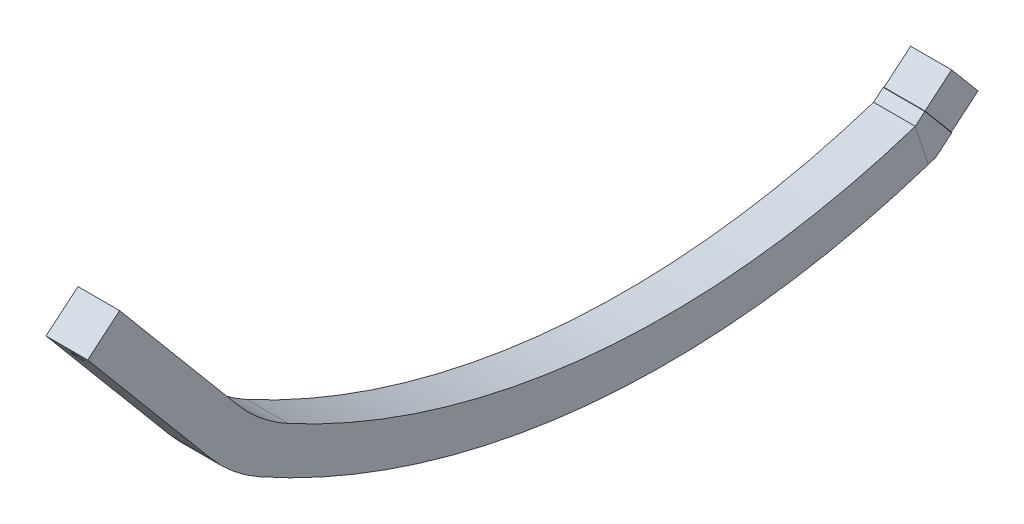
SolidWorks part; units mm, degrees
ref_plane "Ebene vorne" through (0, 0, 0) normal (0, 0, 1) x (1, 0, 0)
ref_plane "Ebene oben" through (0, 0, 0) normal (0, 1, 0) x (1, 0, 0)
ref_plane "Ebene rechts" through (0, 0, 0) normal (1, 0, 0) x (0, 0, -1)
sketch "Skizze1" plane through (0, 0, 0) normal (1, 0, 0) x (0, 0, -1)
  line L0 (0, 12) -> (-233.4212, 12) construction
  line L1 (-240, 65) -> (-230.7357, 72.7737)
  line L2 (0, 12) -> (-3.7358, 23.4037)
  line L3 (0, 12) -> (0, 39.1297) construction
  line L4 (0, 0) -> (-218.6687, 0) construction
  arc A0 (0, 12) -> (-240, 65) centre (-75.176, 241.4765) cw
  arc A1 (-3.7358, 23.4037) -> (-230.7357, 72.7737) centre (-75.176, 241.4765) cw
  dimension "D1" = 53
  dimension "D2" = 240
  dimension "D3" = 40
  dimension "D4" = 12
  dimension "D5" = 12
extrude "Aufsatz-Linear austragen1" add sketch "Skizze1" along normal blind 12
sketch "Skizze4" plane through (0, 0, 0) normal (1, 0, 0) x (0, 0, -1)
  line L0 (-230.7357, 72.7737) -> (-240, 65) construction
  line L2 (-3.7358, 23.4037) -> (6.769, 32.2183)
  line L3 (6.769, 32.2183) -> (14.4825, 23.0258)
  line L4 (14.4825, 23.0258) -> (2.2258, 12.7411)
  line L5 (-3.7358, 23.4037) -> (0, 12)
  arc A0 (0, 12) -> (2.2258, 12.7411) centre (-75.176, 241.4765) ccw
  arc A4 (-240, 65) -> (0, 12) centre (-75.176, 241.4765) ccw construction
  dimension "D1" = 16
  dimension "D2" = 12
extrude "Aufsatz-Linear austragen3" add sketch "Skizze4" along normal blind 12 separate body
sketch "Skizze5" plane through (12, 0, 0) normal (1, 0, 0) x (0, 0, -1)
  line L0 (-231.6625, 71.996) -> (-222.47, 79.7094)
  line L1 (-230.7357, 72.7737) -> (-232.109, 74.04) construction
  line L2 (-231.6625, 71.996) -> (-220.0923, 58.2072)
  line L3 (-230.7357, 72.7737) -> (-240, 65) construction
  line L4 (-222.47, 79.7094) -> (-210.8998, 65.9206)
  line L5 (-220.0923, 58.2072) -> (-192.9483, 44.5269)
  line L6 (-220.0923, 58.2072) -> (-211.3409, 65.5505) construction
  line L7 (-210.8998, 65.9206) -> (-192.9483, 44.5269)
  arc A6 (-230.7357, 72.7737) -> (-3.7358, 23.4037) centre (-75.176, 241.4765) ccw construction
  dimension "D1" = 12
  dimension "D2" = 1.2
  dimension "D3" = 18
extrude "Aufsatz-Linear austragen4" add sketch "Skizze5" against normal up to surface (12 mm away) up to face at (0, 27.378, 122.107)
sketch "Skizze6" plane through (12, 0, 0) normal (1, 0, 0) x (0, 0, -1)
  line L0 (-231.6625, 71.996) -> (-199.5106, 33.6789)
  line L1 (-199.5106, 33.6789) -> (-204.3677, 29.6033)
  line L2 (-204.3677, 29.6033) -> (-240, 65)
  line L3 (-240, 65) -> (-231.6625, 71.996)
extrude "Schnitt-Linear austragen1" cut sketch "Skizze6" against normal through all
sketch "Skizze7" plane through (12, 0, 0) normal (1, 0, 0) x (0, 0, -1)
  line L0 (-222.47, 79.7094) -> (-229.5406, 88.1359)
  line L1 (-192.9483, 44.5269) -> (-222.47, 79.7094) construction
  line L2 (-229.5406, 88.1359) -> (-238.7332, 80.4225)
  line L3 (-238.7332, 80.4225) -> (-231.6625, 71.996)
  line M4 (-222.47, 79.7094) -> (-231.6625, 71.996)
  dimension "D1" = 11
extrude "Aufsatz-Linear austragen5" [suppressed] add sketch "Skizze7" against normal up to surface (12 mm away) contours L2 L3 L0 M4
fillet "Verrundung1" radius 50 2 edges at (6, 35.2854, 200.8587) (6, 44.5269, 192.9483)
sketch "Skizze8" [suppressed] plane through (0, -76.6111, 91.3015) normal (0, 0.6428, -0.766) x (-1, 0, 0)
  line L0 (-6, 215.0619) -> (-6, 184.7045) construction
  line L1 (0, 215.0619) -> (-12, 215.0619) construction
  circle A0 centre (-6, 210.0619) radius 1.55
  dimension "D2" = 3.1
  dimension "D1" = 5
extrude "Schnitt-Linear austragen2" [suppressed] cut sketch "Skizze8" against normal blind 6
sketch "Skizze9" plane through (0, 156.3205, 131.1685) normal (0, 0.766, 0.6428) x (1, 0, 0)
  line L0 (6, -119.1857) -> (6, -131.1857) construction
  line L1 (0, -119.1857) -> (12, -119.1857) construction
  line L2 (0, -131.1857) -> (12, -131.1857) construction
  line L3 (12, -125.1857) -> (0, -125.1857) construction
  line L4 (12, -119.1857) -> (12, -131.1857) construction
  line L5 (0, -119.1857) -> (0, -131.1857) construction
  line L7 (0, -131.1857) -> (12, -131.1857)
  line L8 (0, -131.1857) -> (0, -119.1857)
  line L9 (0, -119.1857) -> (12, -119.1857)
  line L10 (12, -131.1857) -> (12, -119.1857)
  line L11 (0, -131.1857) -> (12, -119.1857) construction
  line L12 (0, -119.1857) -> (12, -131.1857) construction
  point P12 (6, -125.1857)
  dimension "D1" = 12
extrude "Aufsatz-Linear austragen6" add sketch "Skizze9" along normal blind 16
sketch "Skizze10" plane through (0, 16.6449, -19.8366) normal (0, 0.6428, -0.766) x (-1, 0, 0)
  line L0 (-6, 20.3296) -> (-6, 8.3296) construction
  line L1 (-12, 20.3296) -> (0, 20.3296) construction
  line L2 (-12, 8.3296) -> (0, 8.3296) construction
  line L4 (-11.9, 8.4296) -> (-0.1, 8.4296)
  line L5 (-11.9, 8.4296) -> (-11.9, 20.2296)
  line L6 (-11.9, 20.2296) -> (-0.1, 20.2296)
  line L7 (-0.1, 8.4296) -> (-0.1, 20.2296)
  line L8 (-11.9, 8.4296) -> (-0.1, 20.2296) construction
  line L9 (-11.9, 20.2296) -> (-0.1, 8.4296) construction
  circle A0 centre (-6, 14.3296) radius 9.0363
  point P6 (-6, 14.3296)
  dimension "D1" = 11.8
extrude "Schnitt-Linear austragen3" cut sketch "Skizze10" against normal blind 10
sketch "Skizze11" plane through (0, -76.6111, 91.3015) normal (0, 0.6428, -0.766) x (-1, 0, 0)
  line L0 (-6, 220.0619) -> (-6, 204.6824) construction
  line L1 (-12, 220.0619) -> (0, 220.0619) construction
  circle A0 centre (-6, 215.0619) radius 1.55
  dimension "D1" = 3.1
  dimension "D2" = 5
extrude "Schnitt-Linear austragen4" cut sketch "Skizze11" against normal through all
chamfer "Fase1" distance 0.1 angle 45 4 edges at (0, 21.1941, -2.9653) (6, 16.5979, -6.822) (12, 21.1941, -2.9653) (6, 25.7904, 0.8914)
